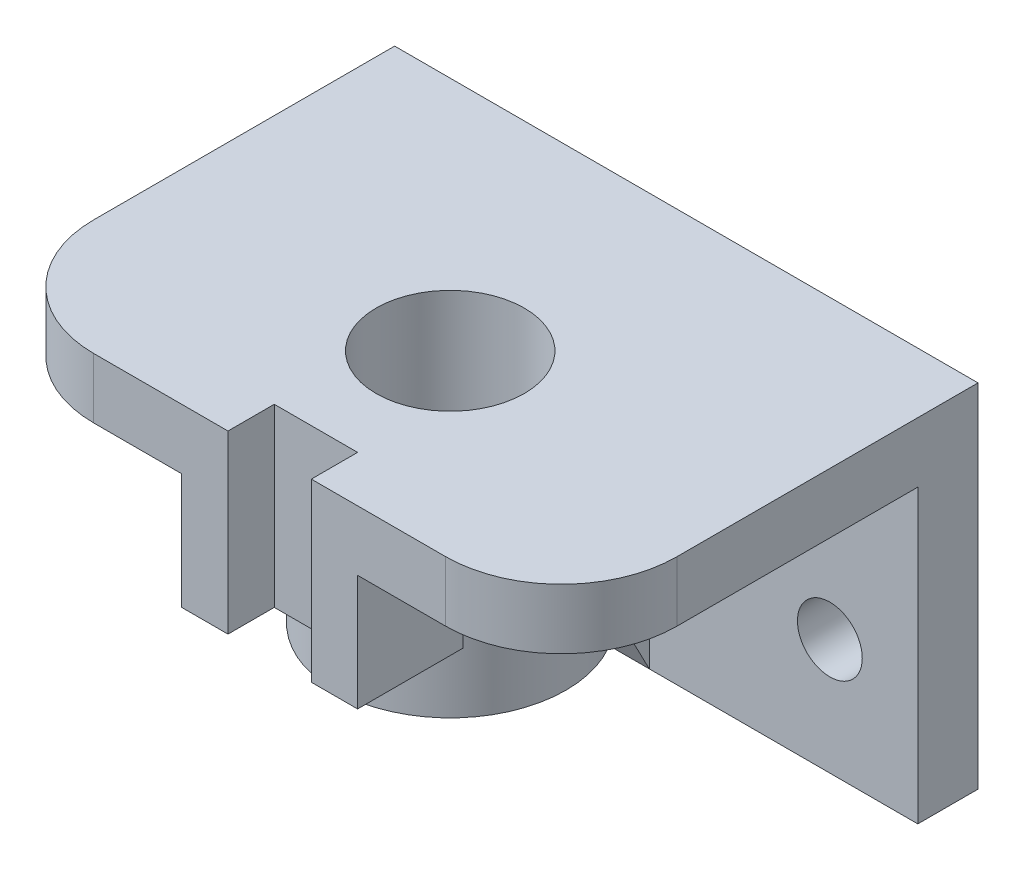
SolidWorks part; units mm, degrees
ref_plane "Front Plane" through (0, 0, 0) normal (0, 0, 1) x (1, 0, 0)
ref_plane "Top Plane" through (0, 0, 0) normal (0, 1, 0) x (1, 0, 0)
ref_plane "Right Plane" through (0, 0, 0) normal (1, 0, 0) x (0, 0, -1)
sketch "Sketch1" plane through (0, 0, 0) normal (0, 0, 1) x (1, 0, 0)
  line L0 (0, 0) -> (0, 76)
  line L1 (0, 76) -> (63, 76)
  line L2 (63, 76) -> (63, 0)
  line L3 (0, 0) -> (63, 0)
  dimension "D1" = 63
  dimension "D2" = 76
extrude "Boss-Extrude1" add sketch "Sketch1" along normal blind 13 contours L3 L2 L1 L0
sketch "Sketch2" plane through (0, 0, 13) normal (0, 0, 1) x (1, 0, 0)
  line L0 (0, 76) -> (0, 63)
  line L1 (0, 0) -> (0, 76) construction
  line L2 (0, 63) -> (63, 63)
  line L3 (63, 76) -> (63, 0) construction
  line L4 (63, 63) -> (63, 76)
  line L5 (63, 76) -> (0, 76)
  line L6 (0, 0) -> (63, 0) construction
  dimension "D1" = 63
extrude "Boss-Extrude2" add sketch "Sketch2" along normal blind 77
fillet "Fillet1" radius 25 1 edges at (0, 69.5, 90)
ref_plane "Plane1" through (0, 25, 0) normal (0, -1, 0) x (-1, 0, 0)
sketch "Sketch4" plane through (0, 25, 0) normal (0, -1, 0) x (-1, 0, 0)
  line L0 (-63, -76) -> (-63, -67)
  line L2 (-63, -26) -> (-63, -35)
  arc A0 (-63, -76) -> (-63, -26) centre (-63, -51) ccw
  arc A1 (-63, -67) -> (-63, -35) centre (-63, -51) ccw
  dimension "D1" = 25
  dimension "D2" = 16
  dimension "D3" = 63
  dimension "D4" = 51
extrude "Boss-Extrude3" add sketch "Sketch4" against normal up to surface (38 mm away) up to face at (29.1645, 63, 55.2355)
sketch "Sketch5" plane through (0, 63, 0) normal (0, -1, 0) x (1, 0, 0)
  line L0 (63, 90) -> (54, 90)
  line L1 (25, 90) -> (63, 90) construction
  line L2 (54, 90) -> (54, 80)
  line L3 (54, 80) -> (63, 80)
  line L4 (63, 90) -> (63, 76) construction
  line L5 (63, 80) -> (63, 90)
  dimension "D1" = 9
  dimension "D2" = 10
extrude "Cut-Extrude1" cut sketch "Sketch5" against normal blind 77
sketch "Sketch6" plane through (0, 0, 90) normal (0, 0, 1) x (1, 0, 0)
  line L0 (54, 63) -> (44, 63)
  line L1 (25, 63) -> (54, 63) construction
  line L2 (44, 63) -> (44, 38)
  line L3 (44, 38) -> (54, 38)
  line L4 (54, 38) -> (54, 63)
  line L5 (54, 76) -> (54, 63) construction
  line L6 (54, 76) -> (25, 76) construction
  dimension "D1" = 10
  dimension "D2" = 38
extrude "Boss-Extrude4" add sketch "Sketch6" against normal up to surface (22.7519 mm away) up to face at (50.5, 44, 51)
sketch "Sketch7" plane through (0, 0, 80) normal (0, 0, 1) x (1, 0, 0)
  line L0 (54, 63) -> (54, 38)
  line L1 (54, 38) -> (63, 38)
  line L2 (63, 38) -> (63, 63)
  line L3 (63, 63) -> (54, 63)
  line L4 (54, 76) -> (54, 63) construction
  line L5 (63, 76) -> (54, 76) construction
  dimension "D1" = 9
  dimension "D2" = 38
extrude "Boss-Extrude5" add sketch "Sketch7" against normal up to surface (4 mm away) up to face at (51.1595, 47.25, 60.2622)
ref_plane "Plane2" through (0, -5.3212, 10.233) normal (0, -0.4614, 0.8872) x (1, 0, 0)
sketch "Sketch8" plane through (0, -5.3212, 10.233) normal (0, -0.4614, 0.8872) x (1, 0, 0)
  line L0 (63, 34.1756) -> (63, 5.9976)
rib "Rib1" sketch "Sketch8" sketch "Sketch8" thickness 5 extrusion direction normal to sketch draft on no parameters "D1"=5
mirror "Mirror1" about plane through (63, 76, 13) normal (1, 0, 0) of bodies 106
sketch "Sketch9" plane through (0, 0, 13) normal (0, 0, 1) x (1, 0, 0)
  line L0 (58, 63) -> (58, 0) construction
  line L2 (0, 63) -> (58, 63) construction
  circle A0 centre (19, 25) radius 7
  dimension "D1" = 14
  dimension "D2" = 39
  dimension "D3" = 38
extrude "Cut-Extrude2" cut sketch "Sketch9" against normal through all
sketch "Sketch10" plane through (0, 25, 0) normal (0, -1, 0) x (1, 0, 0)
  circle A0 centre (63, 51) radius 16
  circle A1 centre (63, 51) radius 16 construction
  dimension "D1" = 32
extrude "Cut-Extrude3" cut sketch "Sketch10" along normal blind 23 from surface starting at face at (63, 76, 66.0355)
sketch "Sketch11" plane through (0, 0, 13) normal (0, 0, 1) x (1, 0, 0)
  line L0 (68, 63) -> (68, 0) construction
  line L2 (126, 0) -> (68, 0) construction
  circle A0 centre (107, 25) radius 7
  dimension "D1" = 14
  dimension "D2" = 39
  dimension "D3" = 25
extrude "Cut-Extrude4" cut sketch "Sketch11" against normal through all
